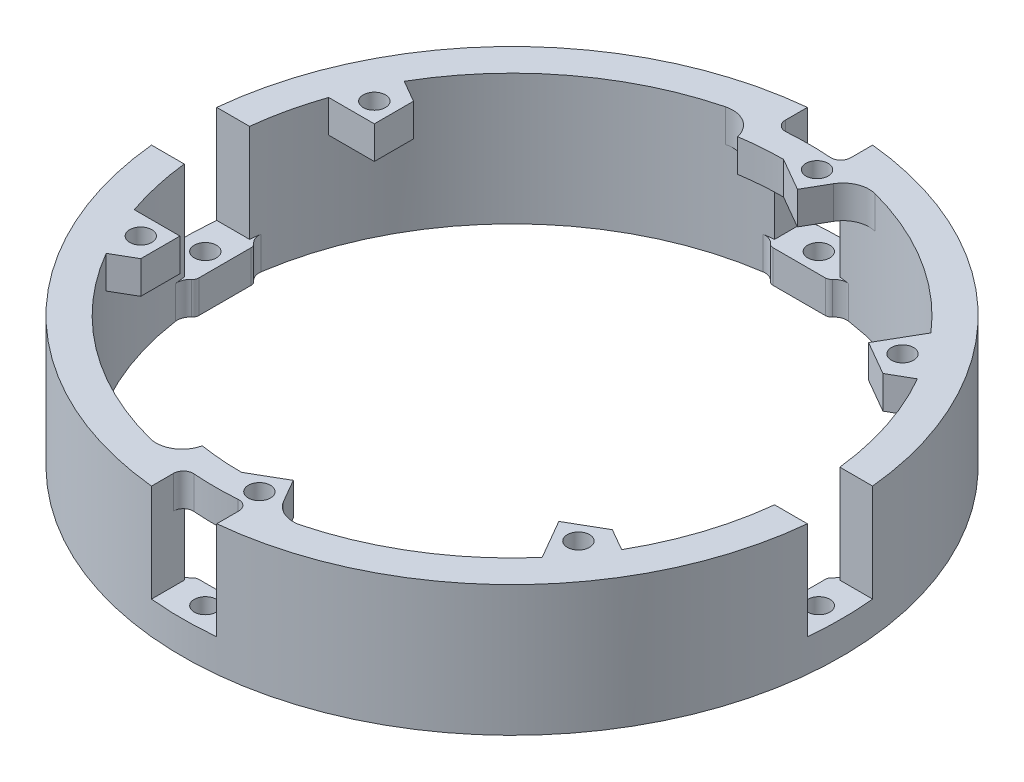
SolidWorks part; units mm, degrees
ref_plane "Front Plane" through (0, 0, 0) normal (0, 0, 1) x (1, 0, 0)
ref_plane "Top Plane" through (0, 0, 0) normal (0, 1, 0) x (1, 0, 0)
ref_plane "Right Plane" through (0, 0, 0) normal (1, 0, 0) x (0, 0, -1)
sketch "Sketch1" plane through (0, 0, 0) normal (0, 1, 0) x (1, 0, 0)
  circle A1 centre (0, 0) radius 50.5
  circle A2 centre (0, 0) radius 45.5
  point P0 (0, 0)
  dimension "D3" = 101
  dimension "D1" = 5
extrude "Boss-Extrude1" add sketch "Sketch1" along normal blind 5
sketch "Sketch3" plane through (0, 0, 0) normal (0, 1, 0) x (-1, 0, 0)
  line L7 (0, 0) -> (45, 0) construction
  line L8 (45, -7.5) -> (45, 7.5) construction
  line L13 (45, 7.5) -> (39, 17.8923) construction
  line L14 (36, -17.8923) -> (39, -17.8923) construction
  line L15 (36, 17.8923) -> (39, 17.8923) construction
  line L16 (36, 20.8923) -> (36, 14.8923)
  line L17 (36, 14.8923) -> (42.9938, 14.8923)
  line L18 (36, 20.8923) -> (40.4198, 20.8923)
  line L19 (45, -7.5) -> (39, -17.8923) construction
  line L23 (40.4198, 20.8923) -> (45.9757, 20.8923)
  line L24 (40.4198, -20.8923) -> (45.9757, -20.8923)
  line L25 (36, -20.8923) -> (40.4198, -20.8923)
  line L26 (36, -20.8923) -> (36, -14.8923)
  line L27 (36, -14.8923) -> (42.9938, -14.8923)
  circle A5 centre (0, 0) radius 50.5 construction
  circle A7 centre (39, 17.8923) radius 1.7
  circle A9 centre (0, 0) radius 45.5 construction
  arc A10 (45.9757, -20.8923) -> (45.9757, 20.8923) centre (0, 0) ccw
  arc A12 (42.9938, -14.8923) -> (42.9938, 14.8923) centre (0, 0) ccw
  circle A13 centre (39, -17.8923) radius 1.7
  point P15 (36, 17.8923)
  dimension "D4" = 150
  dimension "D6" = 6
  dimension "D3" = 12
  dimension "D1" = 45
  dimension "D5" = 3.4
  dimension "D2" = 7.5
  dimension "D7" = 3
extrude "Boss-Extrude2" add sketch "Sketch3" along normal blind 5
sketch "Sketch4" plane through (0, 5, 0) normal (0, 1, 0) x (1, 0, 0)
  line L0 (-36, 20.8923) -> (-39.3531, 22.8382)
  line L1 (-36, -20.8923) -> (-39.3531, -22.8382)
  line L2 (-36, 20.8923) -> (-40.4198, 20.8923)
  line L3 (-36, -20.8923) -> (-40.4198, -20.8923)
  arc A1 (-40.4198, 20.8923) -> (-39.3531, 22.8382) centre (0, 0) cw
  arc A2 (-40.4198, -20.8923) -> (-39.3531, -22.8382) centre (0, 0) ccw
  arc A3 (-40.4198, -20.8923) -> (-40.4198, 20.8923) centre (0, 0) ccw construction
  arc A4 (-40.4198, -20.8923) -> (-40.4198, 20.8923) centre (0, 0) ccw construction
extrude "Boss-Extrude3" add sketch "Sketch4" against normal up to surface (5 mm away) up to face at (-28.4267, 0, 0)
pattern_circular "CirPattern1" count 3 over 360 about axis through (0, 5, 0) along (0, -1, 0) of "Boss-Extrude2", "Boss-Extrude3" reverse direction yes
sketch "Sketch5" plane through (0, 0, 0) normal (0, -1, 0) x (1, 0, 0)
  circle A0 centre (0, 0) radius 50.5
  circle A1 centre (0, 0) radius 45.5
  circle A2 centre (0, 0) radius 50.5 construction
  circle A4 centre (0, 0) radius 45.5 construction
extrude "Boss-Extrude4" add sketch "Sketch5" along normal blind 15
sketch "Sketch6" plane through (0, -15, 0) normal (0, -1, 0) x (1, 0, 0)
  line L0 (0, 0) -> (50.5, 0) construction
  line L1 (50.2519, -5) -> (45, -5)
  line L2 (44, -4) -> (44, 4)
  line L3 (45, 5) -> (50.2519, 5)
  circle A0 centre (0, 0) radius 50.5 construction
  arc A1 (50.2519, -5) -> (50.2519, 5) centre (0, 0) ccw
  circle A2 centre (47, 0) radius 1.7 construction
  arc A3 (45, -5) -> (44, -4) centre (45, -4) cw
  arc A4 (44, 4) -> (45, 5) centre (45, 4) cw
  dimension "D1" = 3.4
  dimension "D5" = 1
  dimension "D2" = 47
  dimension "D3" = 10
  dimension "D4" = 3
extrude "Boss-Extrude5" add sketch "Sketch6" against normal blind 5
sketch "Sketch8" plane through (0, 5, 0) normal (0, 1, 0) x (1, 0, 0)
  line L0 (0, 0) -> (7.8289, 0) construction
  line L1 (44, -5) -> (54, -5)
  line L2 (44, -5) -> (44, 5)
  line L3 (44, 5) -> (54, 5)
  line L4 (54, -5) -> (54, 5)
  line L7 (0, 0) -> (54, 0) construction
  dimension "D1" = 10
  dimension "D2" = 44
  dimension "D3" = 0
extrude "Cut-Extrude1" cut sketch "Sketch8" against normal up to surface (15 mm away) up to face at (44.7184, -10, 0)
sketch "Sketch9" plane through (0, -10, 0) normal (0, 1, 0) x (1, 0, 0)
  line L0 (0, 0) -> (47, 0) construction
  circle A0 centre (47, 0) radius 1.7
  dimension "D1" = 47
  dimension "D2" = 3.4
extrude "Cut-Extrude2" cut sketch "Sketch9" against normal up to next
fillet "Fillet1" radius 2 2 edges at (45.2244, -12.5, -5) (45.2244, -12.5, 5)
pattern_circular "CirPattern2" count 4 over 360 about axis through (0, 5, 0) along (0, -1, 0) of "Boss-Extrude5", "Cut-Extrude1", "Cut-Extrude2", "Fillet1"
sketch "Sketch10" plane through (5, 0, 0) normal (-1, 0, 0) x (0, 0, 1)
  line L0 (45.2244, 0) -> (45.2244, -10) construction
  line L1 (41.2244, 5) -> (45.2244, 5)
  line L2 (41.2244, 5) -> (41.2244, 0)
  line L3 (41.2244, 0) -> (45.2244, 0)
  line L4 (45.2244, 5) -> (45.2244, 0)
  line L5 (45.2244, 0) -> (44.0994, 0) construction
  line L6 (50.2519, 5) -> (44.0994, 5) construction
  dimension "D1" = 4
sketch "Sketch11" plane through (0, 5, 0) normal (0, 1, 0) x (1, 0, 0)
  line L0 (-5, -45.2244) -> (-5, -41.2244) construction
  line L2 (-5, -41.2244) -> (5, -41.2244) construction
  line L3 (5, -41.2244) -> (5, -45.2244) construction
  line L4 (-7, -44.9583) -> (-7, -40.9583) construction
  arc A0 (-39.3531, -22.8382) -> (-5, -45.2244) centre (0, 0) ccw construction
  arc A2 (-7, -42.9459) -> (5, -43.2244) centre (0, 0) ccw
  arc A3 (-39.3531, -22.8382) -> (-5, -45.2244) centre (0, 0) ccw construction
  dimension "D1" = 2
sweep "Sweep5" add profiles "Sketch10" path "Sketch11"
sketch "Sketch16" plane through (0, 5, 0) normal (0, 1, 0) x (1, 0, 0)
  arc A0 (5, -44.0994) -> (5, -41.3429) centre (4.0048, -42.7211) ccw construction
  arc A3 (5, -44.0994) -> (5, -41.3429) centre (4.0048, -42.7211) ccw construction
  circle A4 centre (4.0048, -42.7211) radius 1.7
extrude "Cut-Extrude4" cut sketch "Sketch16" against normal up to surface (5 mm away) up to face at (5.3524, 0, 42.7211)
fillet "Fillet2" radius 1.5 2 edges at (-5, 2.5, 45.2244) (5, 2.5, 45.2244)
fillet "Fillet5" radius 4 2 edges at (8.5998, 2.5, 44.6799) (-7.5464, 2.5, 44.8698)
mirror "Mirror3" about plane through (0, 0, 0) normal (0, 0, 1) of "Sweep5", "Cut-Extrude4"
fillet "Fillet4" radius 1.5 2 edges at (-5, 2.5, -45.2244) (5, 2.5, -45.2244)
fillet "Fillet6" radius 4 2 edges at (-7.5464, 2.5, -44.8698) (8.5998, 2.5, -44.6799)
